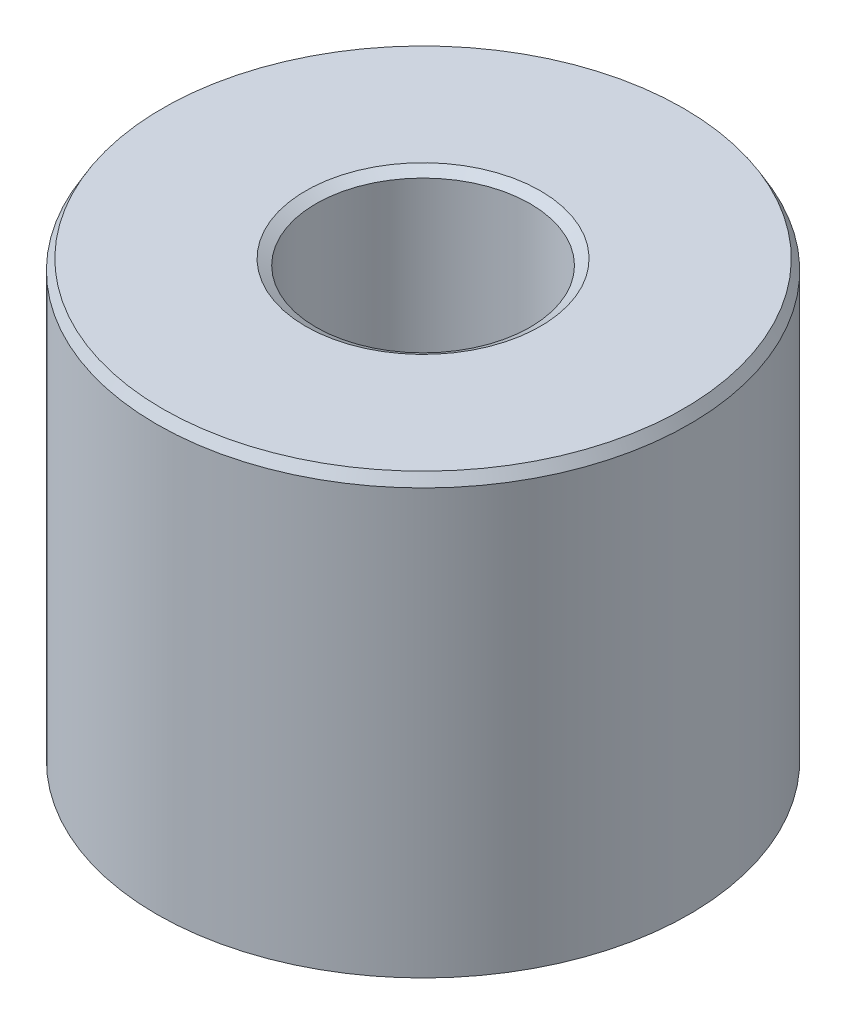
SolidWorks part; units mm, degrees
ref_plane "Front Plane" through (0, 0, 0) normal (0, 0, 1) x (1, 0, 0)
ref_plane "Top Plane" through (0, 0, 0) normal (0, 1, 0) x (1, 0, 0)
ref_plane "Right Plane" through (0, 0, 0) normal (1, 0, 0) x (0, 0, -1)
sketch "Sketch1" plane through (0, 0, 0) normal (0, 1, 0) x (1, 0, 0)
  circle A0 centre (0, 0) radius 25
  dimension "SLEEVE_OD" = 50
extrude "Boss-Extrude1" add sketch "Sketch1" along normal blind 41.3613
sketch "Sketch2" plane through (0, 0, 0) normal (0, 1, 0) x (1, 0, 0)
  circle A0 centre (0, 0) radius 10.0495
  dimension "BORE_D" = 20.0991
extrude "Cut-Extrude1" cut sketch "Sketch2" along normal through all
chamfer "Chamfer1" distance 0.9701 angle 30 4 edges at (0, 41.3613, 10.0495) (0, 0, 10.0495) (0, 0, 25) (0, 41.3613, 25) first distance on face at (0, 41.3613, 10.0495) first distance on face at (0, 0, 10.0495) first distance on face at (0, 41.3613, 25)
